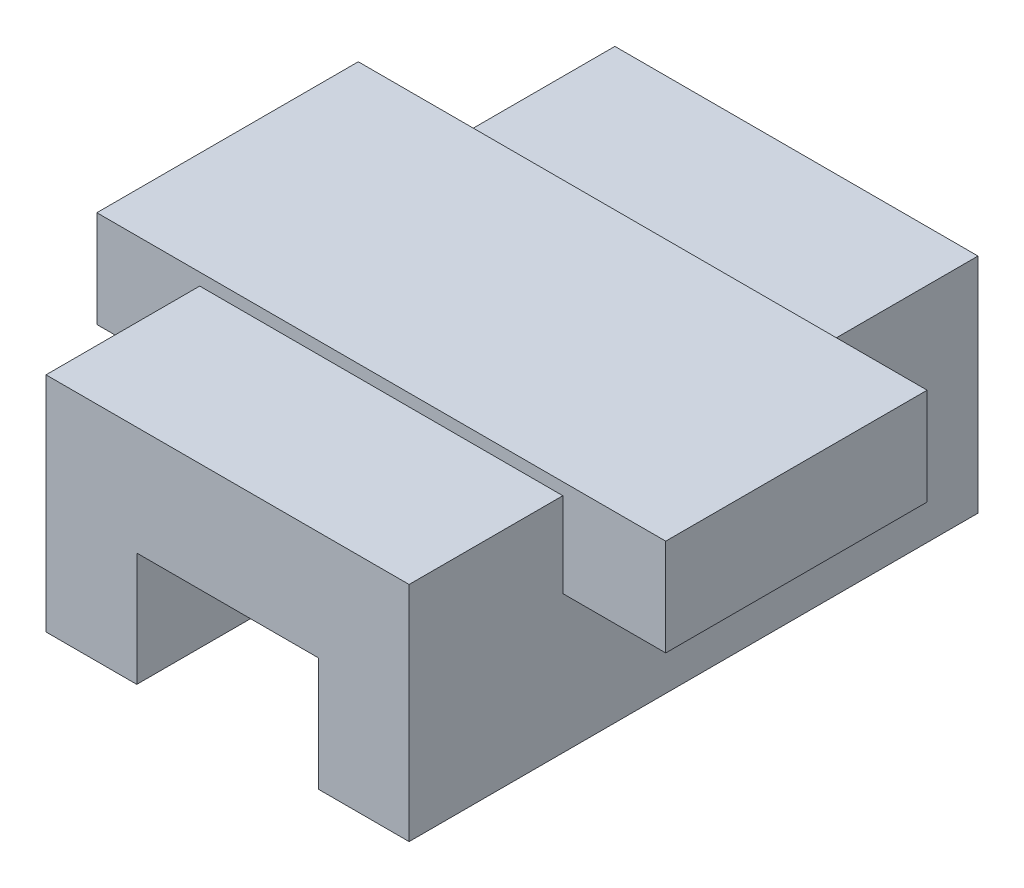
SolidWorks part; units mm, degrees
ref_plane "Front Plane" through (0, 0, 0) normal (0, 0, 1) x (1, 0, 0)
ref_plane "Top Plane" through (0, 0, 0) normal (0, 1, 0) x (1, 0, 0)
ref_plane "Right Plane" through (0, 0, 0) normal (1, 0, 0) x (0, 0, -1)
sketch "Sketch1" plane through (0, 0, 0) normal (0, 0, 1) x (1, 0, 0)
  line L0 (0, -30.2326) -> (0, 30.2326) construction
  line L1 (7.5, -7) -> (-7.5, -7)
  line L2 (7.5, -7) -> (7.5, 7)
  line L3 (7.5, 7) -> (-7.5, 7)
  line L4 (-7.5, -7) -> (-7.5, 7)
  line L5 (7.5, -7) -> (-7.5, 7) construction
  line L6 (7.5, 7) -> (-7.5, -7) construction
  line L8 (15, -2.4) -> (-15, -2.4)
  line L9 (15, -2.4) -> (15, 16)
  line L10 (15, 16) -> (-15, 16)
  line L11 (-15, -2.4) -> (-15, 16)
  line L12 (15, -2.4) -> (-15, 16) construction
  line L13 (15, 16) -> (-15, -2.4) construction
  line L14 (23.5, 9) -> (-23.5, 9)
  line L15 (23.5, 9) -> (23.5, 17)
  line L16 (23.5, 17) -> (-23.5, 17)
  line L17 (-23.5, 9) -> (-23.5, 17)
  line L18 (23.5, 9) -> (-23.5, 17) construction
  line L19 (23.5, 17) -> (-23.5, 9) construction
  point P0 (0, 0)
  point P8 (0, 6.8)
  point P13 (0, 13)
  dimension "D1" = 15
  dimension "D2" = 4.6
  dimension "D3" = 14
  dimension "D4" = 24
  dimension "D5" = 30
  dimension "D6" = 1
  dimension "D7" = 8
  dimension "D8" = 47
extrude "Boss-Extrude1" add sketch "Sketch1" along normal mid plane 47 contours L9 L14 L11 L8 L4 L3 L2 | L14 L9 L10 L11 region at (7.8209, 2.3, 0) region at (0, 12.5, 0)
extrude "Boss-Extrude2" add sketch "Sketch1<3>" along normal mid plane 21.6 contours L17 L14 L11 L10 L9 L15 L16 region at (15.4768, 12.5, 0)
sketch "Sketch1<3>" plane through (0, 0, 0) normal (0, 0, 1) x (1, 0, 0) same geometry as "Sketch1"
